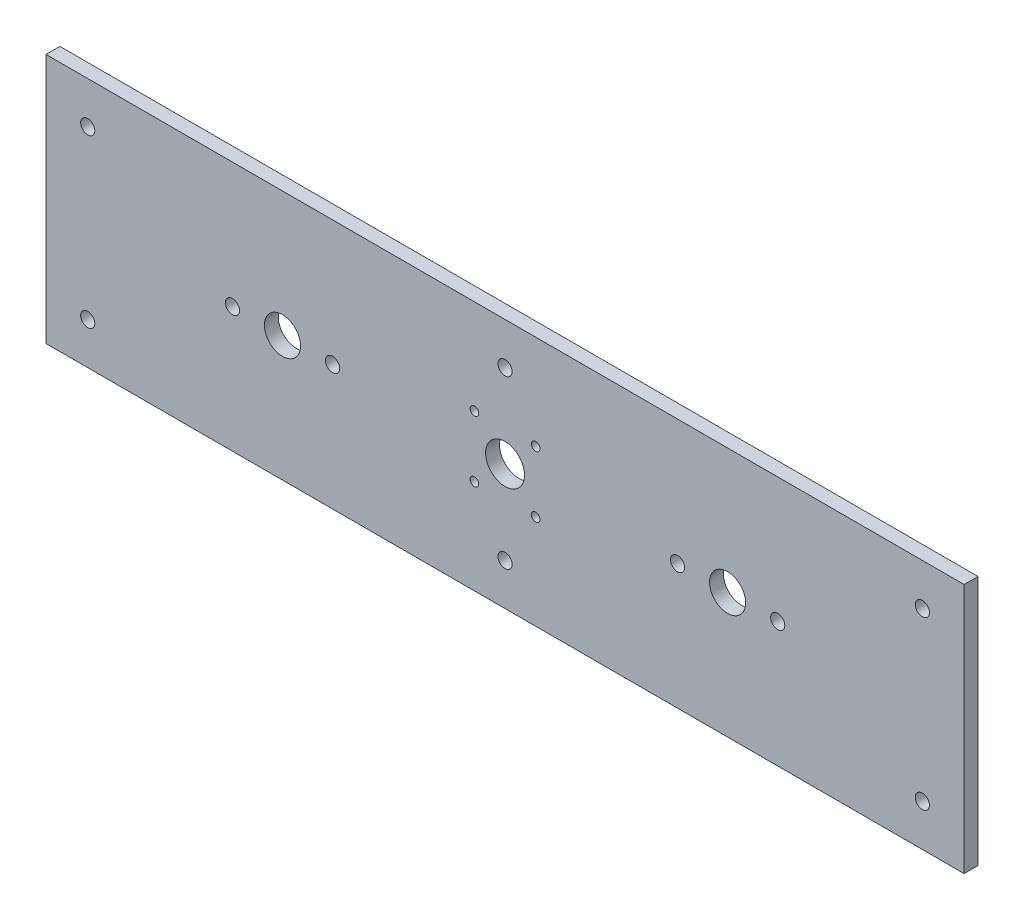
SolidWorks part; units mm, degrees
ref_plane "Front Plane" through (0, 0, 0) normal (0, 0, 1) x (1, 0, 0)
ref_plane "Top Plane" through (0, 0, 0) normal (0, 1, 0) x (1, 0, 0)
ref_plane "Right Plane" through (0, 0, 0) normal (1, 0, 0) x (0, 0, -1)
sketch "Sketch1" plane through (0, 0, 0) normal (0, 0, 1) x (1, 0, 0)
  line L1 (-165, -45) -> (165, -45)
  line L2 (-165, -45) -> (-165, 45)
  line L3 (-165, 45) -> (165, 45)
  line L4 (165, -45) -> (165, 45)
  line L5 (-165, -45) -> (165, 45) construction
  line L6 (-165, 45) -> (165, -45) construction
  point P0 (0, 0)
  dimension "D1" = 330
  dimension "D2" = 90
extrude "Boss-Extrude1" add sketch "Sketch1" along normal mid plane 5
sketch "Sketch2" plane through (0, 0, 2.5) normal (0, 0, 1) x (1, 0, 0)
  line L3 (165, 30) -> (-165, 30)
  line L4 (165, 30) -> (-165, 30) construction
  line L6 (-150, 45) -> (-150, -45)
  line L7 (-150, 45) -> (-150, -45) construction
  line L9 (-165, -30) -> (165, -30)
  line L10 (-165, -30) -> (165, -30) construction
  line L11 (0, 45) -> (0, -45) construction
  line L12 (150, -45) -> (150, 45)
  line L13 (150, -45) -> (150, 45) construction
  line L14 (165, 45) -> (-165, 45) construction
  line L15 (-165, -45) -> (165, -45) construction
  circle A0 centre (150, 30) radius 2.55
  circle A1 centre (150, -30) radius 2.55
  circle A2 centre (0, 30) radius 2.55
  circle A3 centre (0, -30) radius 2.55
  circle A4 centre (-150, -30) radius 2.55
  circle A5 centre (-150, 30) radius 2.55
  dimension "D5" = 5.1
  dimension "D6" = 5.1
  dimension "D7" = 5.1
  dimension "D8" = 5.1
  dimension "D9" = 5.1
  dimension "D10" = 5.1
  dimension "D1" = 15
  dimension "D2" = 15
  dimension "D3" = 15
  dimension "D4" = 15
extrude "Cut-Extrude1" cut sketch "Sketch2" against normal through all
sketch "Sketch3" plane through (0, 0, 2.5) normal (0, 0, 1) x (1, 0, 0)
  line L0 (-165, 0) -> (165, 0) construction
  line L1 (-165, 45) -> (-165, -45) construction
  line L2 (165, -45) -> (165, 45) construction
  circle A0 centre (-80, 0) radius 6.5
  circle A1 centre (-62, 0) radius 2.55
  circle A2 centre (-98, 0) radius 2.55
  dimension "D1" = 13
  dimension "D2" = 5.1
  dimension "D4" = 5.1
  dimension "D3" = 80
  dimension "D5" = 18
  dimension "D6" = 18
extrude "Cut-Extrude2" cut sketch "Sketch3" against normal through all
mirror "Mirror1" about plane through (0, 0, 0) normal (1, 0, 0) of "Cut-Extrude2"
sketch "Sketch4" plane through (0, 0, 2.5) normal (0, 0, 1) x (1, 0, 0)
  line L1 (-11, -11) -> (11, -11) construction
  line L2 (-11, -11) -> (-11, 11) construction
  line L3 (-11, 11) -> (11, 11) construction
  line L4 (11, -11) -> (11, 11) construction
  line L5 (-11, -11) -> (11, 11) construction
  line L6 (-11, 11) -> (11, -11) construction
  circle A0 centre (11, 11) radius 1.55
  circle A1 centre (11, -11) radius 1.55
  circle A2 centre (-11, -11) radius 1.55
  circle A3 centre (-11, 11) radius 1.55
  circle A4 centre (0, 0) radius 7
  point P0 (0, 0)
  dimension "D3" = 3.1
  dimension "D4" = 3.1
  dimension "D5" = 3.1
  dimension "D6" = 3.1
  dimension "D7" = 14
  dimension "D1" = 22
  dimension "D2" = 22
extrude "Cut-Extrude3" cut sketch "Sketch4" against normal through all
equation "\"D3@Sketch3\"=160/2"
